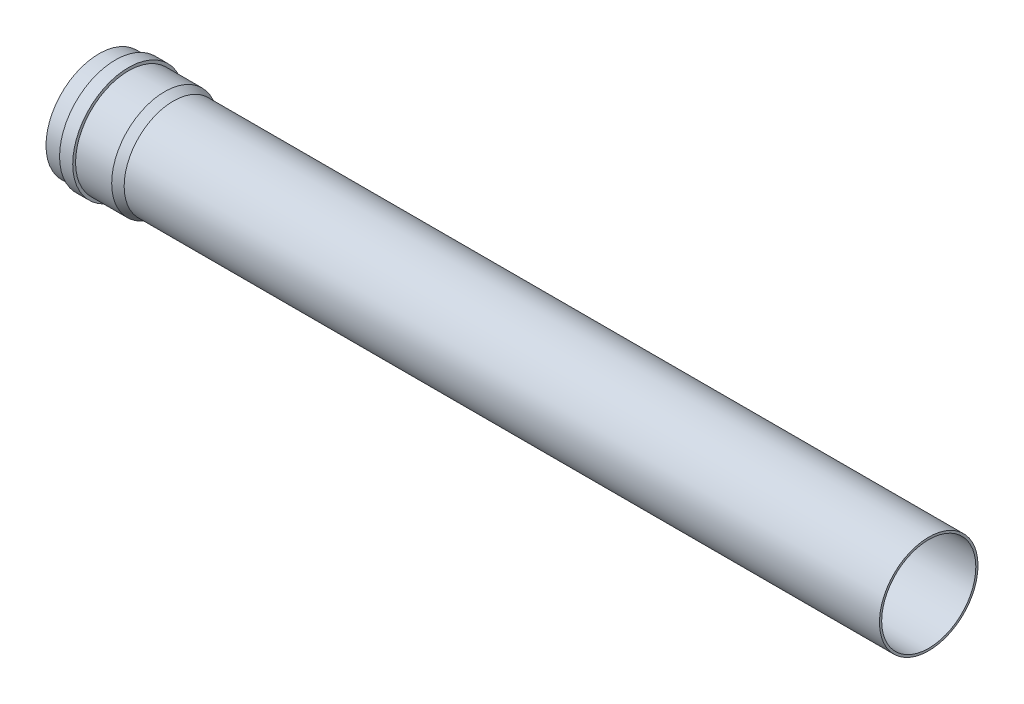
SolidWorks part; units mm, degrees
ref_plane "Plano frontal" through (0, 0, 0) normal (0, 0, 1) x (1, 0, 0)
ref_plane "Plano superior" through (0, 0, 0) normal (0, 1, 0) x (1, 0, 0)
ref_plane "Plano direito" through (0, 0, 0) normal (1, 0, 0) x (0, 0, -1)
sketch "Esboço2" plane through (0, 0, 0) normal (1, 0, 0) x (0, 0, -1)
  circle A0 centre (0, 0) radius 45
  circle A1 centre (0, 0) radius 43
  dimension "D1" = 90
  dimension "D2" = 86
extrude "Ressalto-extrusão1" add sketch "Esboço2" along normal blind 690
sketch "Esboço3" plane through (0, 0, 0) normal (-1, 0, 0) x (0, 0, 1)
  circle A0 centre (0, 0) radius 48.5
  circle A1 centre (0, 0) radius 43
  dimension "D1" = 97
extrude "Ressalto-extrusão2" add sketch "Esboço3" along normal blind 8
chamfer "Chanfro2" distance 3.5 angle 67 1 edges at (0, 0, 48.5) first distance on face at (0, 0, -45)
chamfer "Chanfro3" distance 3.5 angle 66 1 edges at (-8, 0, 43) first distance on face at (-8, 0, 48.3958)
sketch "Esboço4" plane through (-8, 0, 0) normal (-1, 0, 0) x (0, 0, 1)
  circle A0 centre (0, 0) radius 48.3958
  circle A1 centre (0, 0) radius 46.5
extrude "Ressalto-extrusão3" add sketch "Esboço4" along normal blind 60
sketch "Esboço5" plane through (-68, 0, 0) normal (-1, 0, 0) x (0, 0, 1)
  circle A0 centre (0, 0) radius 48.3958
  circle A1 centre (0, 0) radius 51
  circle A3 centre (0, 0) radius 48.3958 construction
  dimension "D2" = 102
extrude "Ressalto-extrusão4" add sketch "Esboço5" against normal blind 27 separate body
sketch "Esboço7" plane through (-68, 0, 0) normal (-1, 0, 0) x (0, 0, 1)
  circle A0 centre (0, 0) radius 48.3958
  circle A1 centre (0, 0) radius 51
extrude "Corte-extrusão1" cut sketch "Esboço7" against normal blind 15
